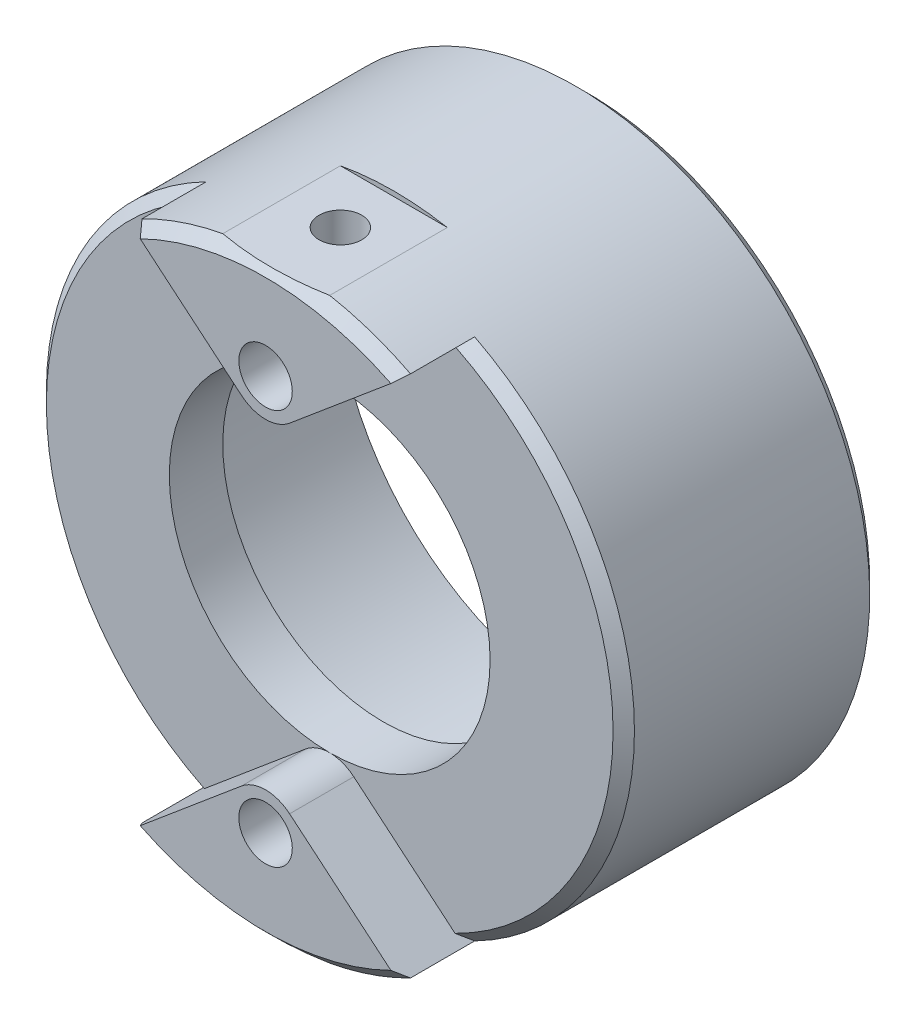
SolidWorks part; units mm, degrees
ref_plane "Front Plane" through (0, 0, 0) normal (1, 0, 0) x (0, 1, 0)
ref_plane "Top Plane" through (0, 0, 0) normal (0, 0, 1) x (0, 1, 0)
ref_plane "Right Plane" through (0, 0, 0) normal (0, 1, 0) x (-1, 0, 0)
sketch "Sketch5" plane through (0, 0, 0) normal (0, 1, 0) x (-1, 0, 0)
  line L1 (-5, 30) -> (5, 30)
  line L2 (-5, 30) -> (-5, 18)
  line L3 (-5, 18) -> (5, 18)
  line L4 (5, 30) -> (5, 18)
  circle A0 centre (0, 23) radius 2
  point P4 (0, 18)
  point P8 (0, 0)
  point P9 (0, 0)
  dimension "D1" = 4
  dimension "D2" = 12
  dimension "D3" = 10
  dimension "D4" = 30
  dimension "D5" = 5
sketch "Sketch4" plane through (0, 0, 0) normal (1, 0, 0) x (0, 1, 0)
  line L0 (0, 29.0382) -> (0, 15.8246) construction
  line L1 (27.5, 0) -> (27.5, 30)
  line L2 (27.5, 30) -> (15, 30)
  line L3 (15, 30) -> (15, 19)
  line L4 (15, 19) -> (23.5, 19)
  line L5 (23.5, 19) -> (23.5, 0)
  line L6 (23.5, 0) -> (27.5, 0)
  point P2 (0, 0)
  point P4 (23.5, -16.914)
  point P11 (0, 0)
  point P12 (27.5, 49.5446)
  point P13 (23.5, 36.672)
  point P15 (23.5, 21.5834)
  dimension "D1" = 47
  dimension "D2" = 30
  dimension "D3" = 55
  dimension "D4" = 1
revolve "Revolve1" add sketch "Sketch4" angle 360 about L0
sketch "Sketch6" plane through (0, 0, 30) normal (0, 0, 1) x (0, -1, 0)
  line L0 (15.8188, -2.2498) -> (24.4665, -12.5556)
  line L2 (16.5, 0) -> (-16.5, 0) construction
  line L3 (15.8188, 2.2498) -> (24.4665, 12.5556)
  line L4 (0, 16.5) -> (0, -16.5) construction
  line L5 (-15.8188, 2.2498) -> (-24.4665, 12.5556)
  line L6 (-15.8188, -2.2498) -> (-24.4665, -12.5556)
  circle A0 centre (0, 0) radius 15 construction
  circle A1 centre (0, 0) radius 27.5 construction
  arc A2 (15.8188, -2.2498) -> (15.8188, 2.2498) centre (18.5, 0) cw
  circle A3 centre (18.5, 0) radius 2.5
  circle A4 centre (-18.5, 0) radius 2.5
  arc A5 (-15.8188, -2.2498) -> (-15.8188, 2.2498) centre (-18.5, 0) ccw
  circle A6 centre (0, 0) radius 27.5
  point P15 (24.1832, 13.0929)
  circle M6 centre (0, 0) radius 15
  circle M7 centre (0, 0) radius 27.5
  dimension "D2" = 5
  dimension "D1" = 100
  dimension "D3" = 37
extrude "Cut-Extrude1" cut sketch "Sketch6" against normal blind 6 contours A5 L6 L0 A2 M7 M6 | A5 A2 L3 L5 M6 M7 region at (-16.5781, 0, 30) region at (16.5781, 0, 30)
extrude "Cut-Extrude4" cut sketch "Sketch6<5>" against normal through all contours A3 | A4 region at (0, -18.5, 30) region at (0, 18.5, 30)
sketch "Sketch6<5>" plane through (0, 0, 30) normal (0, 0, 1) x (0, -1, 0) same geometry as "Sketch6"
chamfer "Chamfer1" distance 1 angle 45 5 edges at (-27.5, 0, 24) (27.5, 0, 24) (0, -27.5, 30) (0, 27.5, 30) (0, -27.5, 0)
sketch "Sketch7" plane through (0, 0, 30) normal (0, 0, 1) x (0, -1, 0)
  line L0 (0, 5) -> (0, -5) construction
  line L1 (-27.5, -5) -> (-27.0416, -5)
  line L2 (-27.5, -5) -> (-27.5, 5)
  line L3 (-27.5, 5) -> (-27.0416, 5)
  line L4 (-27.0416, -5) -> (-27.0416, 5)
  line L5 (0, 16.5) -> (0, -16.5) construction
  line L6 (27.0416, -5) -> (27.0416, 5)
  line L7 (27.5, 5) -> (27.0416, 5)
  line L8 (27.5, -5) -> (27.5, 5)
  line L9 (27.5, -5) -> (27.0416, -5)
  arc A0 (-24.4665, 12.5556) -> (-24.4665, -12.5556) centre (0, 0) ccw construction
  point P6 (-27.5, 0)
  point P11 (-27.0495, 4.9574)
extrude "Cut-Extrude5" cut sketch "Sketch7" against normal up to vertex (12 mm away) up to point (-5, 0, 18)
sketch "Sketch8" plane through (0, 27.0416, 0) normal (0, 1, 0) x (-1, 0, 0)
  circle A0 centre (0, 23) radius 2 construction
  circle A1 centre (0, 23) radius 2
extrude "Cut-Extrude6" cut sketch "Sketch8" against normal blind 5
mirror "Mirror1" about plane through (0, 0, 0) normal (0, 1, 0) of "Cut-Extrude6"
